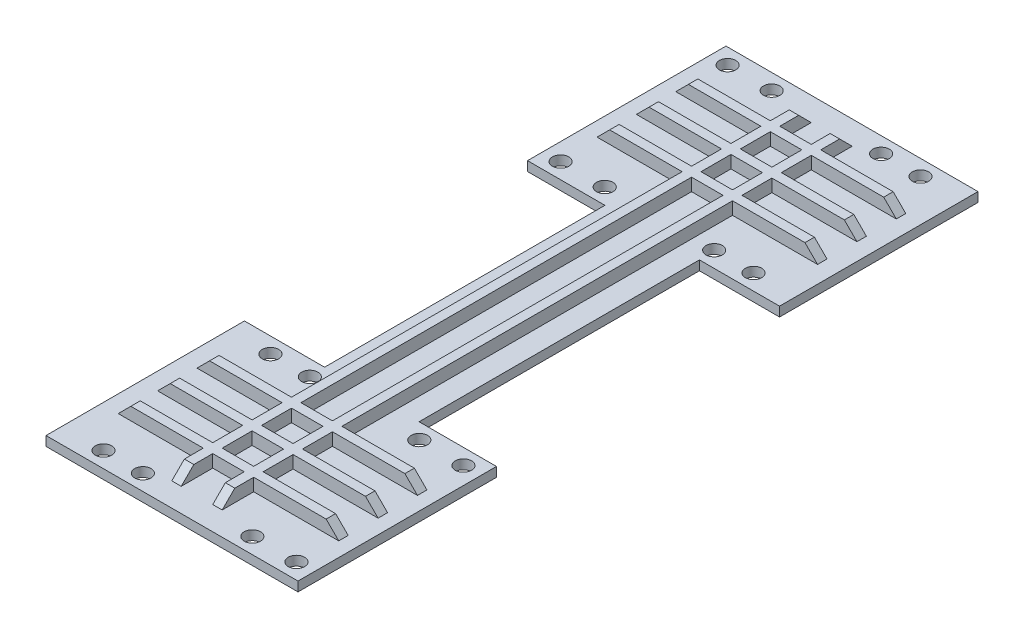
SolidWorks part; units mm, degrees
note: '?' marks a value the reader was unsure of.
ref_plane "Front Plane" through (0, 0, 0) normal (0, 0, 1) x (1, 0, 0)
ref_plane "Top Plane" through (0, 0, 0) normal (0, 1, 0) x (1, 0, 0)
ref_plane "Right Plane" through (0, 0, 0) normal (1, 0, 0) x (0, 0, -1)
sketch "Sketch1" plane through (0, 0, 0) normal (0, 1, 0) x (1, 0, 0)
  line L0 (-40.43, -76) -> (39.57, -76) construction
  line L1 (-39.57, 76) -> (40.43, 76) construction
  line L2 (0, -76) -> (0, 76) construction
  line L3 (39.57, -44.5) -> (39.57, -107.5)
  line L4 (39.57, -107.5) -> (-40.43, -107.5)
  line L5 (-40.43, -107.5) -> (-40.43, -44.5)
  line L6 (-40.43, -44.5) -> (-15, -44.5)
  line L7 (39.57, -44.5) -> (15, -44.5)
  line L8 (-15, 44.5) -> (-39.57, 44.5)
  line L9 (-15, -44.5) -> (-15, 44.5)
  line L11 (15, 44.5) -> (15, -44.5)
  line L12 (-39.57, 44.5) -> (-39.57, 107.5)
  line L13 (-39.57, 107.5) -> (40.43, 107.5)
  line L14 (40.43, 107.5) -> (40.43, 44.5)
  line L15 (40.43, 44.5) -> (15, 44.5)
  point P6 (11.2392, -44.5)
  point P14 (0, 0)
  point P21 (-39.57, 76)
  point P22 (0, 0)
  point P23 (67.4114, 76)
  point P24 (56.0735, 76)
  point P25 (12.9274, 76)
  point P26 (0, 0)
  point P27 (40.43, 76)
  point P28 (0, 0)
  point P29 (0, 0)
  point P30 (0, 0)
  dimension "D1" = 152
  dimension "D2" = 80
  dimension "D3" = 39.57
  dimension "D4" = 63
  dimension "D5" = 30
  dimension "D6" = 63
  dimension "D7" = 80
  dimension "D8" = 39.57
extrude "Boss-Extrude1" add sketch "Sketch1" along normal blind 3
sketch "Sketch2" plane through (0, 3, 0) normal (0, 1, 0) x (1, 0, 0)
  line L0 (-40.43, -76) -> (39.57, -76) construction
  line L1 (34.07, -49.5) -> (20.07, -49.5) construction
  line L2 (34.07, -49.5) -> (34.07, -102.5) construction
  line L3 (34.07, -102.5) -> (20.07, -102.5) construction
  line L4 (20.07, -49.5) -> (20.07, -102.5) construction
  line L5 (-40.43, -44.5) -> (-40.43, -107.5) construction
  line L6 (39.57, -107.5) -> (39.57, -44.5) construction
  line L8 (-27.18, -102.5) -> (-14.68, -102.5) construction
  line L9 (-27.18, -102.5) -> (-27.18, -49.5) construction
  line L10 (-27.18, -49.5) -> (-14.68, -49.5) construction
  line L11 (-14.68, -102.5) -> (-14.68, -49.5) construction
  circle A0 centre (20.07, -49.5) radius 2.6
  circle A1 centre (34.07, -49.5) radius 2.6
  circle A2 centre (34.07, -102.5) radius 2.6
  circle A3 centre (20.07, -102.5) radius 2.6
  circle A4 centre (-14.68, -49.5) radius 2.6
  circle A5 centre (-27.18, -49.5) radius 2.6
  circle A6 centre (-14.68, -102.5) radius 2.6
  circle A7 centre (-27.18, -102.5) radius 2.6
  point P16 (34.07, -76)
  point P23 (-14.68, -76)
  dimension "D1" = 5.2
  dimension "D2" = 5.2
  dimension "D3" = 5.2
  dimension "D4" = 5.2
  dimension "D8" = 5.2
  dimension "D9" = 5.2
  dimension "D10" = 5.2
  dimension "D11" = 5.2
  dimension "D5" = 14
  dimension "D6" = 53
  dimension "D7" = 5.5
  dimension "D12" = 12.5
  dimension "D13" = 53
  dimension "D14" = 13.25
extrude "Cut-Extrude1" cut sketch "Sketch2" against normal through all
ref_axis "Axis1" through (0, 5.25, 0) along (0, -1, 0)?
pattern_circular "CirPattern1" count 2 over 360 about axis through (0, 0, 0) along (0, 1, 0) of "Cut-Extrude1"
sketch "Sketch4" plane through (0, 3, 0) normal (0, 1, 0) x (1, 0, 0)
  line L0 (8, 0) -> (5, 0)
  line L1 (-8, 0) -> (8, 0) construction
  line L2 (-8, 0) -> (-8, -100)
  line L3 (-8, -100) -> (8, -100) construction
  line L4 (8, 0) -> (8, -100)
  line L5 (0, -100) -> (0, 0) construction
  line L7 (5, 0) -> (5, -100)
  line L8 (5, -100) -> (8, -100)
  line L9 (-8, -100) -> (-5, -100)
  line L10 (-5, -100) -> (-5, 0)
  line L11 (-5, 0) -> (-8, 0)
  point P4 (0, 0)
  point P112 (0, 0)
  dimension "D1" = 100
  dimension "D2" = 3
  dimension "D3" = 5
extrude "Boss-Extrude2" add sketch "Sketch4" along normal blind 4
sketch "Sketch5" plane through (0, 7, 0) normal (0, 1, 0) x (1, 0, 0)
  line L0 (5, 0) -> (5, -100) construction
  line L1 (35, -90) -> (-35, -90)
  line L2 (35, -90) -> (35, -87)
  line L3 (35, -87) -> (-35, -87)
  line L4 (-35, -90) -> (-35, -87)
  line L5 (0, -87) -> (0, -90) construction
  line L6 (35, -88.5) -> (-35, -88.5) construction
  line L7 (35, -65) -> (-35, -65)
  line L8 (35, -65) -> (35, -62)
  line L9 (35, -62) -> (-35, -62)
  line L10 (-35, -65) -> (-35, -62)
  line L11 (0, -62) -> (0, -65) construction
  line L12 (35, -63.5) -> (-35, -63.5) construction
  line L13 (-5, -100) -> (-5, 0) construction
  line L14 (-5, -100) -> (-5, 0) construction
  line L15 (35, -88.5) -> (35, -63.5) construction
  line L16 (-35, -88.5) -> (-35, -63.5) construction
  line L17 (-40.43, -76) -> (39.57, -76) construction
  line L18 (39.57, -107.5) -> (39.57, -44.5) construction
  line L19 (-40.43, -44.5) -> (-40.43, -107.5) construction
  line L21 (-35, -74.5) -> (35, -74.5)
  line L22 (-35, -74.5) -> (-35, -77.5)
  line L23 (-35, -77.5) -> (35, -77.5)
  line L24 (35, -74.5) -> (35, -77.5)
  line L25 (0, -77.5) -> (0, -74.5) construction
  line L26 (-35, -76) -> (35, -76) construction
  point P26 (-35, -76)
  point P67 (0, -76)
  point P86 (0, -63.5)
  point P144 (0, -88.5)
  dimension "D1" = 3
  dimension "D2" = 3
  dimension "D3" = 25
  dimension "D4" = 70
  dimension "D5" = 3
extrude "Boss-Extrude3" add sketch "Sketch5" against normal up to body
chamfer "Chamfer2" distance 4 angle 45 8 edges at (35, 7, 63.5) (35, 7, 76) (35, 7, 88.5) (6.5, 7, 100) (-6.5, 7, 100) (-35, 7, 88.5) (-35, 7, 76) (-35, 7, 63.5)
pattern_circular "CirPattern2" count 2 over 360 about axis through (0, 0, 0) along (0, 1, 0) of "Boss-Extrude3", "Chamfer2", "Boss-Extrude2"
